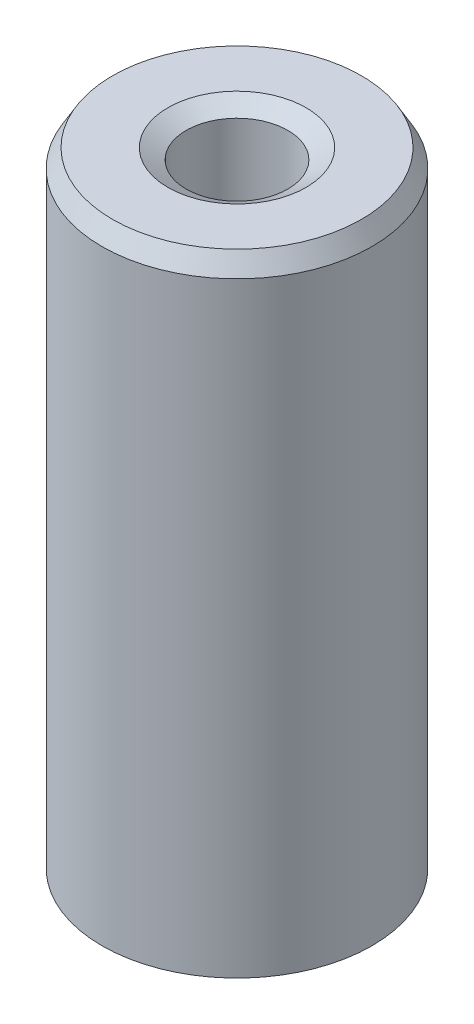
SolidWorks part; units mm, degrees
ref_plane "Front Plane" through (0, 0, 0) normal (0, 0, 1) x (1, 0, 0)
ref_plane "Top Plane" through (0, 0, 0) normal (0, 1, 0) x (1, 0, 0)
ref_plane "Right Plane" through (0, 0, 0) normal (1, 0, 0) x (0, 0, -1)
sketch "Sketch1" plane through (0, 0, 0) normal (0, 1, 0) x (1, 0, 0)
  circle A0 centre (0, 0) radius 25
  dimension "SLEEVE_OD" = 50
extrude "Boss-Extrude1" add sketch "Sketch1" along normal blind 117.4745
sketch "Sketch2" plane through (0, 0, 0) normal (0, 1, 0) x (1, 0, 0)
  circle A0 centre (0, 0) radius 9.4173
  dimension "BORE_D" = 18.8346
extrude "Cut-Extrude1" cut sketch "Sketch2" along normal through all
chamfer "Chamfer1" distance 3.3797 angle 30 4 edges at (0, 117.4745, 9.4173) (0, 0, 9.4173) (0, 0, 25) (0, 117.4745, 25) first distance on face at (0, 117.4745, 9.4173) first distance on face at (0, 0, 9.4173) first distance on face at (0, 117.4745, 25)
